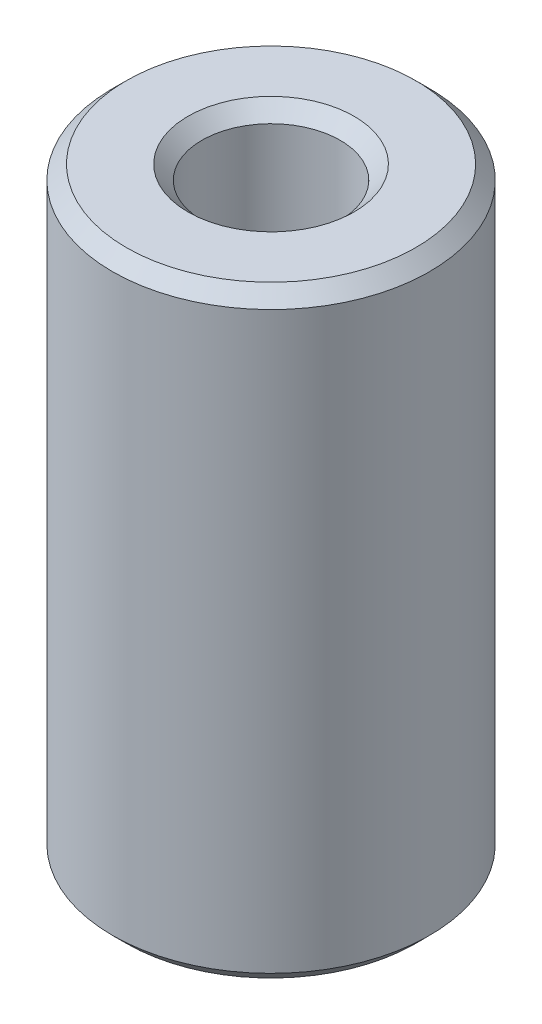
SolidWorks part; units mm, degrees
ref_plane "Front Plane" through (0, 0, 0) normal (0, 0, 1) x (1, 0, 0)
ref_plane "Top Plane" through (0, 0, 0) normal (0, 1, 0) x (1, 0, 0)
ref_plane "Right Plane" through (0, 0, 0) normal (1, 0, 0) x (0, 0, -1)
sketch "Sketch1" plane through (0, 0, 0) normal (0, 1, 0) x (1, 0, 0)
  circle A0 centre (0, 0) radius 40
  dimension "SLEEVE_OD" = 80
extrude "Boss-Extrude1" add sketch "Sketch1" along normal blind 152.0334
sketch "Sketch2" plane through (0, 0, 0) normal (0, 1, 0) x (1, 0, 0)
  circle A0 centre (0, 0) radius 17.4447
  dimension "BORE_D" = 34.8894
extrude "Cut-Extrude1" cut sketch "Sketch2" along normal through all
chamfer "Chamfer1" distance 3.5 angle 45 4 edges at (0, 152.0334, 17.4447) (0, 0, 17.4447) (0, 0, 40) (0, 152.0334, 40)
